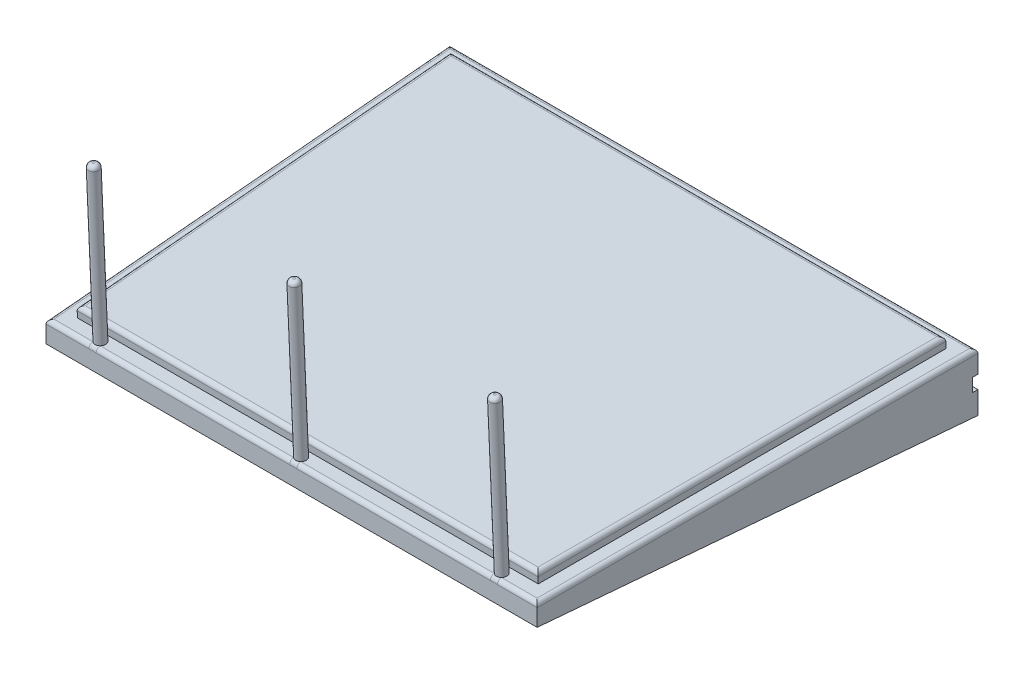
SolidWorks part; units mm, degrees
ref_plane "Plan de face" through (0, 0, 0) normal (0, 0, 1) x (1, 0, 0)
ref_plane "Plan de dessus" through (0, 0, 0) normal (0, 1, 0) x (1, 0, 0)
ref_plane "Plan de droite" through (0, 0, 0) normal (1, 0, 0) x (0, 0, -1)
sketch "Esquisse1" plane through (0, 0, 0) normal (0, 0, 1) x (1, 0, 0)
  line L1 (-50, -7.5) -> (50, -7.5)
  line L2 (-50, -7.5) -> (-50, 7.5)
  line L3 (-50, 7.5) -> (50, 7.5)
  line L4 (50, -7.5) -> (50, 7.5)
  line L5 (-50, -7.5) -> (50, 7.5) construction
  line L6 (-50, 7.5) -> (50, -7.5) construction
  point P0 (0, 0)
  dimension "D1" = 100
  dimension "D2" = 15
extrude "Boss.-Extru.1" add sketch "Esquisse1" along normal blind 80 draft 2.5
sketch "Esquisse2" plane through (49.9049, 0, 2.1789) normal (0.999, 0, 0.0436) x (0.0436, 0, -0.999)
  line L0 (2.181, -1.25) -> (1.181, -1.25)
  line L1 (2.181, -7.5) -> (2.181, 7.5) construction
  line L2 (1.181, -1.25) -> (1.181, 1.25)
  line L3 (1.181, 1.25) -> (2.181, 1.25)
  line L4 (2.181, 1.25) -> (2.181, -1.25)
  point P6 (2.181, 0)
  point P7 (2.181, 0)
  dimension "D1" = 1
  dimension "D2" = 2.5
extrude "Enlèv. mat.-Extru.1" cut sketch "Esquisse2" against normal through all
mirror "Symétrie1" about plane through (0, 0, 0) normal (1, 0, 0) of "Enlèv. mat.-Extru.1"
sketch "Esquisse3" plane through (0, 7.4857, 0.3268) normal (0, 0.999, 0.0436) x (1, 0, 0)
  line L0 (46.8663, -2.6729) -> (-46.8663, -2.6729)
  line L1 (-46.8663, -2.6729) -> (-43.6351, -76.7491)
  line L2 (-43.6351, -76.7491) -> (43.6351, -76.7491)
  line L3 (43.6351, -76.7491) -> (46.8663, -2.6729)
  line L12 (53.1337, 3.3271) -> (-53.1337, 3.3271)
  line L13 (-53.1337, 3.3271) -> (-49.3791, -82.7491)
  line L14 (-49.3791, -82.7491) -> (49.3791, -82.7491)
  line L15 (49.3791, -82.7491) -> (53.1337, 3.3271)
extrude "Enlèv. mat.-Extru.2" cut sketch "Esquisse3" against normal blind 2
mirror "Symétrie2" about plane through (0, 0, 0) normal (0, 1, 0) of "Enlèv. mat.-Extru.2"
sketch "Esquisse4" plane through (0, -3.3477, 76.676) normal (0, -0.0436, 0.999) x (1, 0, 0)
  line L0 (-37.6205, 5.4929) -> (-37.6205, 35.4929)
  line L1 (-43.6351, 5.4929) -> (43.6351, 5.4929) construction
  dimension "D1" = 30
sketch "Esquisse5" plane through (0, 5.4876, 0.2396) normal (0, 0.999, 0.0436) x (1, 0, 0)
  line L0 (-46.5071, -79.8364) -> (46.5071, -79.8364) construction
  circle A0 centre (-37.6917, -78.3364) radius 1
  dimension "D1" = 2
  dimension "D2" = 1.5
sweep "Balayage1" add profiles "Esquisse5" path "Esquisse4"
pattern_linear "Répétition linéaire1" count 3 spacing 38 along (1, 0, 0) of "Balayage1"
fillet "Congé1" radius 0.8 3 edges at (38.3083, 31.9985, 80.8091) (0.3083, 31.9985, 80.8091) (-37.6917, 31.9985, 80.8091)
fillet "Congé2" radius 0.8 8 edges at (0, 4.138, 77.0029) (0, 2.0052, 80) (-48.2536, 3.7517, 40) (-45.2507, 5.7536, 40) (45.2507, 5.7536, 40) (0, 7.3691, 2.9971) (0, 5.4981, 0) (48.2536, 3.7517, 40)
